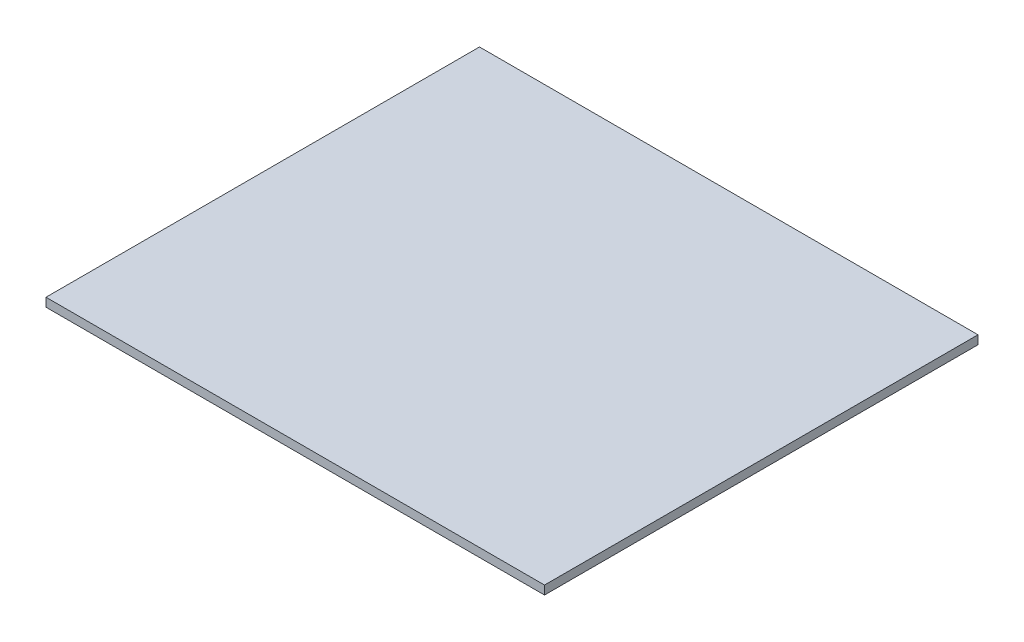
SolidWorks part; units mm, degrees
ref_plane "Front Plane" through (0, 0, 0) normal (0, 0, 1) x (1, 0, 0)
ref_plane "Top Plane" through (0, 0, 0) normal (0, 1, 0) x (1, 0, 0)
ref_plane "Right Plane" through (0, 0, 0) normal (1, 0, 0) x (0, 0, -1)
sketch "Sketch1" plane through (0, 0, 0) normal (0, 1, 0) x (1, 0, 0)
  line L1 (-115, -100) -> (115, -100)
  line L2 (-115, -100) -> (-115, 100)
  line L3 (-115, 100) -> (115, 100)
  line L4 (115, -100) -> (115, 100)
  line L5 (-115, -100) -> (115, 100) construction
  line L6 (-115, 100) -> (115, -100) construction
  point P0 (0, 0)
  dimension "D1" = 230
  dimension "D2" = 200
extrude "Boss-Extrude1" add sketch "Sketch1" along normal blind 4
